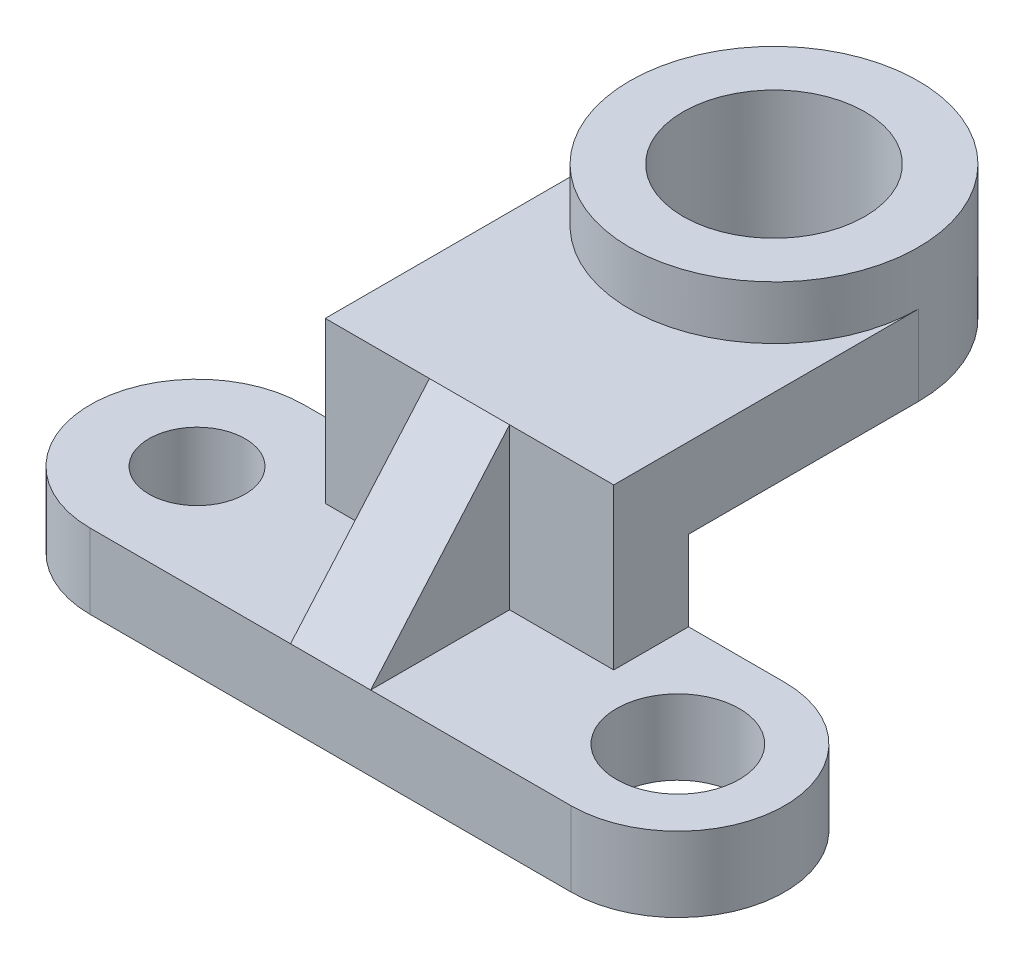
SolidWorks part; units mm, degrees
ref_plane "前视基准面" through (0, 0, 0) normal (0, 0, 1) x (1, 0, 0)
ref_plane "上视基准面" through (0, 0, 0) normal (0, 1, 0) x (1, 0, 0)
ref_plane "右视基准面" through (0, 0, 0) normal (1, 0, 0) x (0, 0, -1)
other "Configuration Table"
sketch "草图1" plane through (0, 0, 0) normal (0, 1, 0) x (1, 0, 0)
  line L0 (0, 0) -> (180, 0) construction
  line L1 (0, 40) -> (180, 40)
  line L2 (0, -40) -> (180, -40)
  arc A0 (0, 40) -> (0, -40) centre (0, 0) ccw
  arc A1 (180, -40) -> (180, 40) centre (180, 0) ccw
  circle A2 centre (180, 0) radius 23
  circle A3 centre (0, 0) radius 18
  point P3 (90, 0)
  dimension "D3" = 36
  dimension "D4" = 46
  dimension "D1" = 180
  dimension "D2" = 80
extrude "凸台-拉伸1" add sketch "草图1" along normal blind 28
sketch "草图2" plane through (0, 28, 0) normal (0, 1, 0) x (1, 0, 0)
  line L0 (180, 40) -> (0, 40) construction
  line L1 (144, 40) -> (144, 126)
  line L2 (90, 40) -> (144, 40)
  line L3 (90, 40) -> (36, 40)
  line L4 (0, -40) -> (180, -40) construction
  line L5 (36, 126) -> (36, 40)
  circle A0 centre (90, 126) radius 34
  circle A1 centre (90, 126) radius 54
  line M10 (180, 40) -> (0, 40)
  dimension "D4" = 108
  dimension "D5" = 68
  dimension "D1" = 54
  dimension "D2" = 54
  dimension "D3" = 166
extrude "凸台-拉伸3" add sketch "草图2" along normal blind 60 separate body contours A1 L5 L1 M10 region at (90, 28, -63.4606)
extrude "凸台-拉伸4" add sketch "草图2<5>" along normal blind 80 contours A1 A0 region at (90, 28, -73.5274)
sketch "草图2<5>" plane through (0, 28, 0) normal (0, 1, 0) x (1, 0, 0) same geometry as "草图2"
sketch "草图4" plane through (0, 28, 0) normal (0, -1, 0) x (1, 0, 0)
  line L3 (36, -40) -> (36, -126)
  line L4 (144, -126) -> (144, -40)
  line L5 (144, -40) -> (36, -40)
  line L6 (36, -40) -> (36, -126)
  line L7 (144, -126) -> (144, -40)
  line L8 (144, -40) -> (36, -40)
  arc A1 (36, -126) -> (144, -126) centre (90, -126) ccw
  arc A2 (36, -126) -> (144, -126) centre (90, -126) ccw
  dimension "D1" = 0
extrude "切除-拉伸1" cut sketch "草图4" against normal blind 30
sketch "草图6" plane through (0, 28, 0) normal (0, 1, 0) x (1, 0, 0)
  line L0 (144, 40) -> (36, 40)
  line L1 (36, 40) -> (36, 12)
  line L2 (36, 12) -> (144, 12)
  line L3 (144, 12) -> (144, 40)
  dimension "D1" = 28
extrude "凸台-拉伸5" add sketch "草图6" along normal up to surface (60 mm away) up to face at (90, 88, -69.5)
ref_plane "基准面1" through (90, 0, 0) normal (-1, 0, 0) x (0, 0, 1)
sketch "草图7" plane through (90, 0, 0) normal (-1, 0, 0) x (0, 0, 1)
  line L0 (40, 28) -> (-12, 28)
  line L1 (-12, 88) -> (-12, 28) construction
  line L2 (40, 28) -> (-40, 28) construction
  line L3 (-12, 28) -> (-12, 88)
  line L4 (-12, 88) -> (40, 28)
extrude "凸台-拉伸6" add sketch "草图7" along normal mid plane 30
